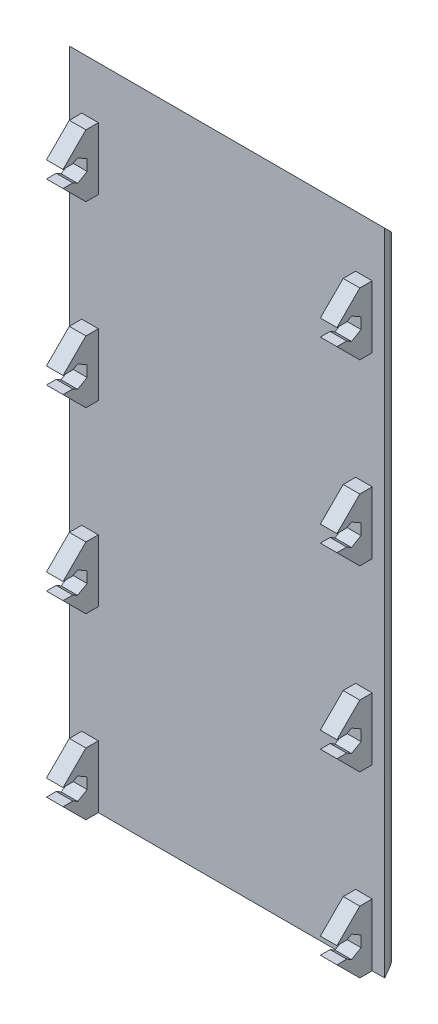
SolidWorks part; units mm, degrees
ref_plane "Front Plane" through (0, 0, 0) normal (0, 0, 1) x (1, 0, 0)
ref_plane "Top Plane" through (0, 0, 0) normal (0, 1, 0) x (1, 0, 0)
ref_plane "Right Plane" through (0, 0, 0) normal (1, 0, 0) x (0, 0, -1)
sketch "Sketch1" plane through (0, 0, 0) normal (0, 1, 0) x (1, 0, 0)
  line L0 (-9.2151, 0) -> (-9.2151, -10)
  line L1 (-9.2151, -10) -> (-5.2151, -10)
  line L2 (-5.2151, -10) -> (-5.2151, 0)
  line L3 (-5.2151, 0) -> (56.7849, 0)
  line L4 (56.7849, 0) -> (56.7849, -10)
  line L5 (56.7849, -10) -> (60.7849, -10)
  line L6 (60.7849, -10) -> (60.7849, 0)
  line L7 (60.7849, 0) -> (63.7849, 0)
  line L8 (-9.2151, 0) -> (-12.2151, 0)
  line L9 (-12.2151, 0) -> (-8.1737, 7)
  line L10 (-8.1737, 7) -> (59.7434, 7)
  line L11 (59.7434, 7) -> (63.7849, 0)
  line L12 (25.7849, 7) -> (25.7849, 0) construction
  dimension "D1" = 3
  dimension "D2" = 10
  dimension "D3" = 70
  dimension "D4" = 7
  dimension "D5" = 4
  dimension "D6" = 60
extrude "Boss-Extrude1" add sketch "Sketch1" along normal blind 156.5
sketch "Sketch4" plane through (60.7849, 0, 0) normal (1, 0, 0) x (0, 0, -1)
  line L0 (0, 156.5) -> (0, 0) construction
  line L1 (-37.5185, 156.5) -> (0, 156.5)
  line L2 (-37.5185, 156.5) -> (-37.5185, 144)
  line L3 (-37.5185, 144) -> (0, 144)
  line L4 (0, 156.5) -> (0, 144)
  line L5 (-37.5185, 156.5) -> (0, 144) construction
  line L6 (-37.5185, 144) -> (0, 156.5) construction
  line L7 (-10, 156.5) -> (0, 156.5) construction
  point P0 (-18.7592, 150.25)
  dimension "D1" = 12.5
extrude "Cut-Extrude1" cut sketch "Sketch4" against normal through all
sketch "Sketch5" plane through (60.7849, 0, 0) normal (1, 0, 0) x (0, 0, -1)
  line L0 (0, 156.5) -> (0, 0) construction
  line L1 (-33.3149, 129) -> (0, 129)
  line L2 (-33.3149, 129) -> (-33.3149, 101)
  line L3 (-33.3149, 101) -> (0, 101)
  line L4 (0, 129) -> (0, 101)
  line L5 (-33.3149, 129) -> (0, 101) construction
  line L6 (-33.3149, 101) -> (0, 129) construction
  line L7 (-10, 144) -> (0, 144) construction
  point P0 (-16.6574, 115)
  dimension "D1" = 28
  dimension "D2" = 15
extrude "Cut-Extrude2" cut sketch "Sketch5" against normal through all
sketch "Sketch6" plane through (0, 0, 0) normal (1, 0, 0) x (0, 0, -1)
  line L0 (-10, 144) -> (-10, 129) construction
  line L1 (-2.7, 137.8279) -> (-5, 139.1558)
  line L2 (-5, 139.1558) -> (-7.3, 137.8279)
  line L3 (-7.3, 137.8279) -> (-7.3, 135.1721)
  line L4 (-7.3, 135.1721) -> (-5, 133.8442)
  line L5 (-5, 133.8442) -> (-2.7, 135.1721)
  line L6 (-2.7, 135.1721) -> (-2.7, 137.8279)
  line L7 (-10, 144) -> (0, 144) construction
  line L8 (-6.15, 138.4919) -> (-10, 138.4919)
  line L9 (-6.15, 134.5081) -> (-10, 134.5081)
  line L10 (-10, 134.5081) -> (-10, 138.4919)
  circle A1 centre (-5, 136.5) radius 2.3 construction
  dimension "D1" = 4.6
  dimension "D2" = 7.5
  dimension "D3" = 5
extrude "Cut-Extrude3" cut sketch "Sketch6" against normal through all and the other way through all contours L10 L9 L4 L3 L2 L8 | L5 L6 L1 L2 L3 L4 region at (0, 136.5, 5) region at (0, 136.5, 8.5351)
pattern_linear "LPattern1" count 4 spacing 43 along (0, -1, 0) of "Cut-Extrude2", "Cut-Extrude3"
chamfer "Chamfer3" distance 7 angle 45 1 edges at (25.7849, 156.5, -7)
fillet "Fillet1" radius 8 2 edges at (-8.1737, 74.75, -7) (59.7434, 74.75, -7)
chamfer "Chamfer5" distance 7 angle 45 16 edges at (58.7849, 43, 10) (58.7849, 144, 10) (58.7849, 129, 10) (-7.2151, 144, 10) (-7.2151, 129, 10) (-7.2151, 101, 10) (-7.2151, 86, 10) (58.7849, 101, 10) (58.7849, 86, 10) (58.7849, 58, 10) (58.7849, 0, 10) (58.7849, 15, 10) (-7.2151, 0, 10) (-7.2151, 15, 10) (-7.2151, 58, 10) (-7.2151, 43, 10)
sketch "Sketch7" plane through (0, 0, -7) normal (0, 0, -1) x (-1, 0, 0)
  line L8 (3.5549, 82.737) -> (-11.316, 82.737) construction
  line L14 (-11.316, 128.6101) -> (-40.2538, 128.6101) construction
  line L20 (-11.316, 128.6101) -> (-11.316, 82.737) construction
  line L22 (-40.2538, 128.6101) -> (-40.2538, 82.737) construction
  line L23 (-11.316, 82.737) -> (-40.2538, 82.737) construction
  line L24 (3.5549, 0) -> (3.5549, 149.5) construction
  line L25 (-11.316, 127.6101) -> (-11.316, 116.1874)
  line L26 (-12.316, 128.6101) -> (-39.2538, 128.6101)
  line L27 (-11.316, 115.6101) -> (-40.2538, 115.6101) construction
  line L28 (-40.2538, 127.6101) -> (-40.2538, 115.6101)
  line L29 (-40.2538, 82.737) -> (-55.1246, 82.737) construction
  line L30 (-55.1246, 149.5) -> (-55.1246, 0) construction
  line L31 (-11.316, 149.5) -> (-11.316, 128.6101) construction
  line L32 (3.5549, 149.5) -> (-55.1246, 149.5) construction
  line L35 (-11.316, 107.5272) -> (-17.816, 103.7744)
  line L38 (-25.316, 99.4443) -> (-39.7538, 91.1086)
  line L39 (-11.316, 107.5272) -> (-11.316, 93.237)
  line L40 (-40.2538, 90.2426) -> (-40.2538, 82.737)
  line L41 (-40.2538, 82.737) -> (-32.316, 87.3199)
  line L42 (-32.316, 87.3199) -> (-32.316, 93.237) construction
  line L43 (-18.316, 102.9084) -> (-18.316, 93.237)
  line L44 (-11.316, 93.237) -> (-32.316, 93.237) construction
  line L45 (-25.316, 99.4443) -> (-25.316, 93.237)
  line L46 (-18.316, 93.237) -> (-25.316, 93.237) construction
  line L47 (-39.7538, 107.2744) -> (-18.566, 119.5072)
  line L48 (-40.2538, 115.6101) -> (-40.2538, 106.9857) construction
  line L49 (-11.316, 82.737) -> (-40.2538, 82.737) construction
  line L50 (-40.2538, 106.4084) -> (-40.2538, 100.5631)
  line L51 (-32.316, 87.3199) -> (-30.9714, 88.0962)
  line L52 (-11.816, 115.3214) -> (-31.566, 103.9187)
  line L53 (-33.2538, 121.1101) -> (-33.2538, 119.3988)
  line L54 (-31.566, 103.0527) -> (-25.316, 99.4443)
  line L55 (-32.316, 95.4028) -> (-39.7538, 99.6971)
  line L56 (-33.5038, 118.9657) -> (-40.2538, 115.0686)
  line L57 (-40.2538, 115.0686) -> (-40.2538, 115.6101)
  line L58 (-32.7538, 121.6101) -> (-18.816, 121.6101)
  line L59 (-18.316, 121.1101) -> (-18.316, 119.9402)
  line L60 (-11.316, 121.6101) -> (-18.316, 121.6101) construction
  line L61 (-33.2538, 121.6101) -> (-40.2538, 121.6101) construction
  line L62 (-40.2538, 128.6101) -> (-11.316, 128.6101) construction
  line L63 (-11.316, 128.6101) -> (-11.316, 82.737) construction
  arc A7 (-11.316, 93.237) -> (-32.316, 93.237) centre (-21.816, 93.237) cw
  arc A8 (-18.316, 93.237) -> (-25.316, 93.237) centre (-21.816, 93.237) cw
  arc A9 (-17.816, 103.7744) -> (-18.316, 102.9084) centre (-17.316, 102.9084) ccw
  arc A10 (-11.816, 115.3214) -> (-11.316, 116.1874) centre (-12.316, 116.1874) ccw
  arc A11 (-11.316, 127.6101) -> (-12.316, 128.6101) centre (-12.316, 127.6101) ccw
  arc A12 (-39.7538, 91.1086) -> (-40.2538, 90.2426) centre (-39.2538, 90.2426) ccw
  arc A13 (-39.2538, 128.6101) -> (-40.2538, 127.6101) centre (-39.2538, 127.6101) ccw
  arc A14 (-40.2538, 106.4084) -> (-39.7538, 107.2744) centre (-39.2538, 106.4084) cw
  arc A15 (-39.7538, 99.6971) -> (-40.2538, 100.5631) centre (-39.2538, 100.5631) cw
  arc A16 (-32.7538, 121.6101) -> (-33.2538, 121.1101) centre (-32.7538, 121.1101) ccw
  arc A17 (-33.5038, 118.9657) -> (-33.2538, 119.3988) centre (-33.7538, 119.3988) ccw
  arc A18 (-18.316, 121.1101) -> (-18.816, 121.6101) centre (-18.816, 121.1101) ccw
  arc A19 (-18.566, 119.5072) -> (-18.316, 119.9402) centre (-18.816, 119.9402) ccw
  arc A20 (-31.566, 103.0527) -> (-31.566, 103.9187) centre (-31.316, 103.4857) cw
  point P59 (-40.2538, 106.9857)
  point P63 (-40.2538, 99.9857)
  dimension "D11" = 7
  dimension "D12" = 30
  dimension "D10" = 7
  dimension "D14" = 0.5
  dimension "D16" = 7
  dimension "D6" = 7
  dimension "D13" = 1
  dimension "D2" = 1
  dimension "0.5" = 1
  dimension "D18" = 1
  dimension "D4" = 0.5
  dimension "D1" = 7
  dimension "D3" = 7
  dimension "D5" = 7
  dimension "D7" = 7
  dimension "D8" = 7
  dimension "D9" = 7
  dimension "D15" = 30
  dimension "D17" = 7
extrude "Cut-Extrude4" cut sketch "Sketch7" against normal blind 1 contours L54 A20 L52 A10 L25 A11 L26 A13 L28 L57 L56 L53 L58 L59 L47 A14 L50 A15 L55 L38 | L38 A12 L40 L41 L51 A7 L39 L35 A9 L43 A8 L45 region at (11.7564, 121.8988, -7) region at (25.697, 96.3406, -7)
sketch "Sketch8" plane through (0, 0, -7) normal (0, 0, -1) x (-1, 0, 0)
  line L0 (-40.2538, 128.6101) -> (-40.2538, 50.6101) construction
  line L1 (-55.1246, 149.5) -> (-55.1246, 0) construction
  line L2 (-25.7849, 128.6101) -> (-55.1246, 128.6101) construction
  line L3 (-12.316, 128.6101) -> (-39.2538, 128.6101) construction
  line L5 (-40.2538, 127.6101) -> (-40.2538, 115.0686) construction
  text T0 "DREam" font "VALORANT" height in points 14
  dimension "D1" = 78
extrude "Cut-Extrude5" cut sketch "Sketch8" against normal blind 1
fillet "Fillet2" radius 0.5 2 edges at (32.316, 95.4028, -6.5) (25.316, 99.4443, -6.5)
sketch "Sketch9" plane through (0, 0, -7) normal (0, 0, -1) x (-1, 0, 0)
  line L0 (-10.0874, 71.5072) -> (-21.5874, 71.5072)
  line L1 (-21.5874, 71.5072) -> (-21.5874, 69.0072)
  line L2 (-21.5874, 69.0072) -> (-10.0874, 69.0072)
  line L3 (-10.0874, 69.0072) -> (-10.0874, 64.7572)
  line L4 (-10.0874, 64.7572) -> (-7.5874, 64.7572)
  line L5 (-7.5874, 64.7572) -> (-7.5874, 75.7572)
  line L6 (-7.5874, 75.7572) -> (-10.0874, 75.7572)
  line L7 (-10.0874, 75.7572) -> (-10.0874, 71.5072)
  line L8 (-7.5874, 62.2572) -> (-7.5874, 59.7572)
  line L9 (-7.5874, 59.7572) -> (-21.5874, 59.7572)
  line L10 (-21.5874, 59.7572) -> (-21.5874, 62.2572)
  line L11 (-21.5874, 62.2572) -> (-7.5874, 62.2572)
  line L12 (-7.5874, 75.7572) -> (-7.5874, 12.6828) construction
  line L13 (-21.5874, 71.5072) -> (-21.5874, 10.6582) construction
  line L14 (-7.5874, 57.2572) -> (-21.5874, 57.2572)
  line L15 (-21.5874, 57.2572) -> (-21.5874, 54.7572)
  line L16 (-21.5874, 54.7572) -> (-12.5874, 54.7572)
  line L17 (-12.5874, 54.7572) -> (-21.5874, 49.5611)
  line L18 (-21.5874, 49.5611) -> (-21.5874, 47.0611)
  line L19 (-21.5874, 47.0611) -> (-12.5874, 47.0611)
  line L20 (-12.5874, 47.0611) -> (-21.5874, 41.8649)
  line L21 (-21.5874, 41.8649) -> (-21.5874, 41.4782)
  line L22 (-21.5874, 41.4782) -> (-17.2573, 41.4782)
  line L23 (-17.2573, 41.4782) -> (-7.5874, 47.0611)
  line L24 (-7.5874, 47.0611) -> (-7.5874, 49.5611)
  line L25 (-7.5874, 49.5611) -> (-16.5874, 49.5611)
  line L26 (-16.5874, 49.5611) -> (-7.5874, 54.7572)
  line L27 (-7.5874, 54.7572) -> (-7.5874, 57.2572)
  line L28 (-7.5874, 47.0611) -> (-21.5874, 38.9782) construction
  line L29 (-21.5874, 38.9782) -> (-7.5874, 38.9782)
  line L30 (-7.5874, 38.9782) -> (-7.5874, 36.4782)
  line L31 (-7.5874, 36.4782) -> (-21.5874, 28.3953)
  line L32 (-21.5874, 28.3953) -> (-21.5874, 31.282)
  line L33 (-21.5874, 31.282) -> (-19.3374, 32.5811)
  line L34 (-19.3374, 32.5811) -> (-21.5874, 36.4782)
  line L35 (-21.5874, 36.4782) -> (-21.5874, 38.9782)
  line L36 (-12.5874, 36.4782) -> (-17.1723, 33.8311)
  line L38 (-18.7006, 36.4782) -> (-12.5874, 36.4782)
  line L39 (-18.7006, 36.4782) -> (-17.1723, 33.8311)
  line L40 (-7.5874, 30.8953) -> (-12.2573, 30.8953)
  line L41 (-12.2573, 30.8953) -> (-16.5874, 28.3953)
  line L42 (-16.5874, 28.3953) -> (-12.5874, 28.3953)
  line L43 (-12.5874, 28.3953) -> (-21.5874, 23.1991)
  line L44 (-21.5874, 23.1991) -> (-21.5874, 20.6991)
  line L45 (-21.5874, 20.6991) -> (-7.5874, 20.6991)
  line L46 (-7.5874, 20.6991) -> (-7.5874, 23.1991)
  line L47 (-7.5874, 23.1991) -> (-16.5874, 23.1991)
  line L48 (-16.5874, 23.1991) -> (-7.5874, 28.3953)
  line L49 (-7.5874, 28.3953) -> (-7.5874, 30.8953)
  line L50 (-7.5874, 18.1991) -> (-7.5874, 15.6991)
  line L51 (-7.5874, 15.6991) -> (-13.5874, 15.6991)
  line L52 (-13.5874, 15.6991) -> (-13.5874, 9.6991)
  line L53 (-13.5874, 9.6991) -> (-7.5874, 9.6991)
  line L54 (-7.5874, 9.6991) -> (-7.5874, 7.1991)
  line L55 (-7.5874, 7.1991) -> (-21.5874, 7.1991)
  line L56 (-21.5874, 7.1991) -> (-21.5874, 9.6991)
  line L57 (-21.5874, 9.6991) -> (-16.0874, 9.6991)
  line L58 (-16.0874, 9.6991) -> (-16.0874, 15.6991)
  line L59 (-16.0874, 15.6991) -> (-21.5874, 15.6991)
  line L60 (-21.5874, 15.6991) -> (-21.5874, 18.1991)
  line L61 (-21.5874, 18.1991) -> (-7.5874, 18.1991)
  dimension "D1" = 2.5
  dimension "D2" = 14
  dimension "D3" = 11
  dimension "D4" = 2.5
  dimension "D5" = 2.5
  dimension "D6" = 2.5
  dimension "D7" = 30
  dimension "D8" = 2.5
  dimension "D9" = 2.5
  dimension "D10" = 60
  dimension "D11" = 2.5
  dimension "D12" = 2.5
  dimension "D13" = 30
  dimension "D14" = 60
  dimension "D15" = 2.5
  dimension "D16" = 2.5
  dimension "D17" = 2.5
  dimension "D18" = 2.5
  dimension "D19" = 2.5
  dimension "D20" = 2.5
  dimension "D21" = 2.5
  dimension "D22" = 30
  dimension "D23" = 2.5
  dimension "D24" = 11
  dimension "D25" = 6
  dimension "D26" = 2.5
extrude "Cut-Extrude6" cut sketch "Sketch9" against normal blind 1
